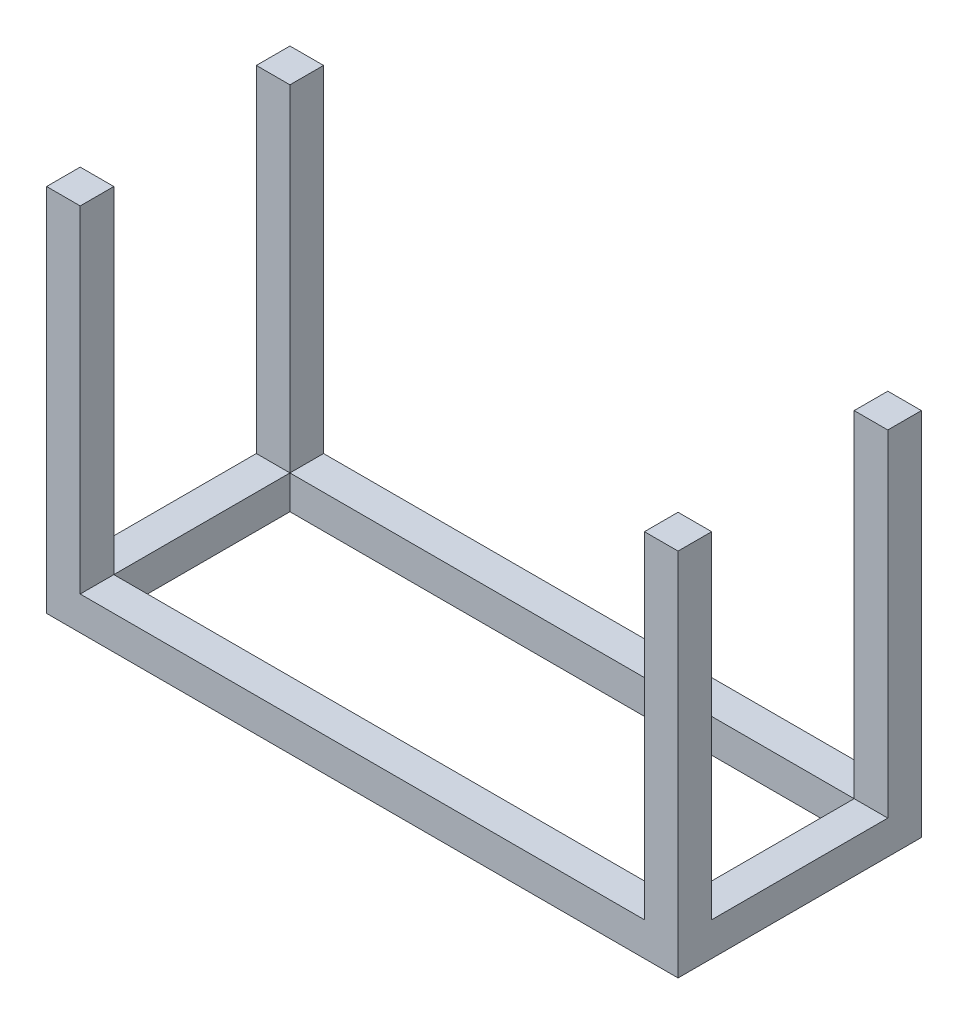
SolidWorks part; units mm, degrees
ref_plane "Front Plane" through (0, 0, 0) normal (0, 0, 1) x (1, 0, 0)
ref_plane "Top Plane" through (0, 0, 0) normal (0, 1, 0) x (1, 0, 0)
ref_plane "Right Plane" through (0, 0, 0) normal (1, 0, 0) x (0, 0, -1)
sketch "Sketch1" plane through (0, 0, 0) normal (0, 1, 0) x (1, 0, 0)
  line L1 (-62.95, -19.65) -> (62.95, -19.65)
  line L2 (-62.95, -19.65) -> (-62.95, 19.65)
  line L3 (-62.95, 19.65) -> (62.95, 19.65)
  line L4 (62.95, -19.65) -> (62.95, 19.65)
  line L7 (-70.45, -27.15) -> (70.45, -27.15)
  line L8 (-70.45, -27.15) -> (-70.45, 27.15)
  line L9 (-70.45, 27.15) -> (70.45, 27.15)
  line L10 (70.45, -27.15) -> (70.45, 27.15)
  point P0 (0, 0)
  point P6 (0, 0)
  dimension "D1" = 125.9
  dimension "D2" = 39.3
  dimension "D3" = 140.9
  dimension "D4" = 54.3
extrude "Boss-Extrude1" add sketch "Sketch1" along normal blind 7.5
sketch "Sketch2" plane through (0, 7.5, 0) normal (0, 1, 0) x (1, 0, 0)
  line L0 (70.45, 27.15) -> (-70.45, 27.15) construction
  line L1 (-70.45, 27.15) -> (-62.95, 27.15)
  line L2 (-70.45, 27.15) -> (-70.45, 19.65)
  line L3 (-70.45, 19.65) -> (-62.95, 19.65)
  line L4 (-62.95, 27.15) -> (-62.95, 19.65)
  line L5 (62.95, 19.65) -> (70.45, 19.65)
  line L6 (62.95, 19.65) -> (62.95, 27.15)
  line L7 (62.95, 27.15) -> (70.45, 27.15)
  line L8 (70.45, 19.65) -> (70.45, 27.15)
  line L9 (70.45, -27.15) -> (70.45, 27.15) construction
  line L10 (-62.95, -19.65) -> (62.95, -19.65) construction
  line L11 (62.95, -19.65) -> (70.45, -19.65)
  line L12 (62.95, -19.65) -> (62.95, -27.15)
  line L13 (62.95, -27.15) -> (70.45, -27.15)
  line L14 (70.45, -19.65) -> (70.45, -27.15)
  line L15 (62.95, -19.65) -> (62.95, 19.65) construction
  line L16 (-70.45, -27.15) -> (70.45, -27.15) construction
  line L17 (-62.95, -19.65) -> (-70.45, -19.65)
  line L18 (-62.95, -19.65) -> (-62.95, -27.15)
  line L19 (-62.95, -27.15) -> (-70.45, -27.15)
  line L20 (-70.45, -19.65) -> (-70.45, -27.15)
  line L21 (-70.45, 27.15) -> (-70.45, -27.15) construction
  line L22 (-62.95, 23.4) -> (62.95, 23.4) construction
  line L23 (62.95, 23.4) -> (66.7, 19.65) construction
  line L24 (66.7, 19.65) -> (66.7, -19.65) construction
  line L25 (66.7, -19.65) -> (62.95, -23.4) construction
  line L26 (62.95, -23.4) -> (-62.95, -23.4) construction
  line L27 (-62.95, -23.4) -> (-66.7, -19.65) construction
  line L28 (-66.7, -19.65) -> (-66.7, 19.65) construction
  line L29 (-66.7, 19.65) -> (-62.95, 23.4) construction
  dimension "D1" = 7.5
  dimension "D2" = 7.5
  dimension "D3" = 125.9
  dimension "D4" = 39.3
extrude "Boss-Extrude2" add sketch "Sketch2" along normal blind 75
